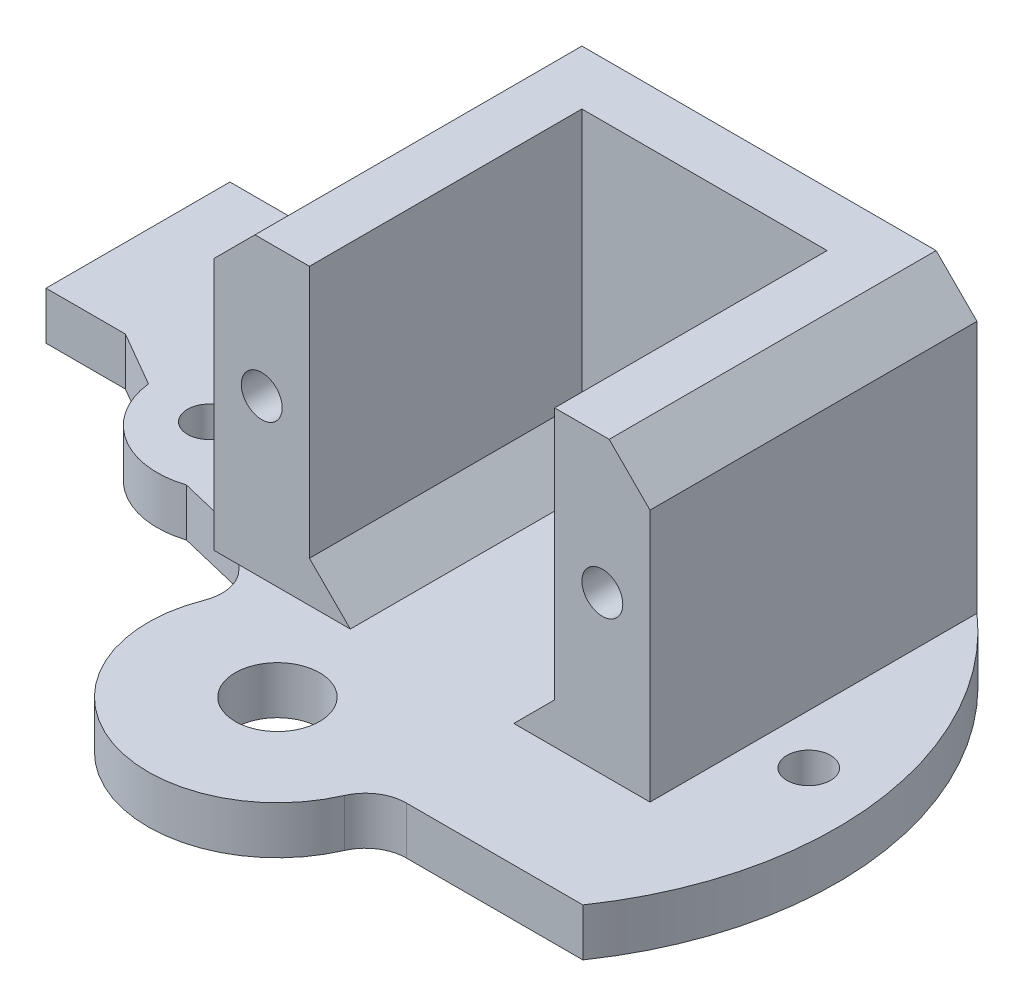
SolidWorks part; units mm, degrees
ref_plane "Alzado" through (0, 0, 0) normal (0, 0, 1) x (1, 0, 0)
ref_plane "Planta" through (0, 0, 0) normal (0, 1, 0) x (1, 0, 0)
ref_plane "Vista lateral" through (0, 0, 0) normal (1, 0, 0) x (0, 0, -1)
sketch "Croquis1" plane through (0, 0, 0) normal (0, 1, 0) x (1, 0, 0)
  line L0 (-35, 32.5) -> (35, -32.5) construction
  line L1 (-35, 32.5) -> (35, 32.5)
  line L2 (-35, 32.5) -> (-35, -32.5)
  line L3 (-35, -32.5) -> (35, -32.5)
  line L4 (35, 32.5) -> (35, -32.5)
  dimension "D1" = 70
  dimension "D2" = 65
extrude "Extruir1" add sketch "Croquis1" along normal blind 3.5
sketch "Croquis2" plane through (0, 3.5, 0) normal (0, 1, 0) x (1, 0, 0)
  line L0 (0, 32.5) -> (0, -32.5) construction
  line L1 (35, 32.5) -> (-35, 32.5) construction
  line L2 (-35, -32.5) -> (35, -32.5) construction
  circle A0 centre (0, -17.5) radius 3.1
  dimension "D1" = 6.2
  dimension "D2" = 15
extrude "Extruir2" cut sketch "Croquis2" against normal blind 5
sketch "Croquis3" plane through (0, 3.5, 0) normal (0, 1, 0) x (1, 0, 0)
  line L0 (0, -32.5) -> (0, 32.5) construction
  line L1 (-35, -32.5) -> (35, -32.5) construction
  line L2 (35, 32.5) -> (-35, 32.5) construction
  line L3 (-32.9868, -32.5) -> (-32.9868, 32.5) construction
  line L4 (-32.9868, 1.5) -> (-12.9615, 1.5)
  line L5 (18.8496, -32.5) -> (18.8496, 32.5) construction
  line L6 (-32.9868, 3.5) -> (18.8496, 3.5) construction
  line L7 (-32.9868, 2) -> (0, 2) construction
  line L8 (-32.9868, 11.5) -> (18.8496, 11.5) construction
  line L9 (0, -17.5) -> (-14.8492, -2.6508) construction
  line L10 (0, -17.5) -> (14.8492, -2.6508) construction
  line L11 (0, 2) -> (18.8496, 2) construction
  line L12 (-32.9868, 2) -> (18.8496, 2) construction
  line L13 (-32.9868, 12) -> (18.8496, 12)
  line L14 (-5.3033, -12.1967) -> (-16.2635, -1.2365) construction
  line L15 (12.9615, 1.5) -> (18.8496, 1.5)
  line L16 (-32.9868, 1.5) -> (18.8496, 1.5) construction
  line L17 (7.9844, -18) -> (22.9946, -18)
  line L18 (-5.9993, -12.2078) -> (-16.6132, -1.5939)
  line L19 (0, -17.5) -> (23, -17.5) construction
  line L20 (7.5, -17.5) -> (23, -17.5) construction
  line L21 (-5.6569, -12.5503) -> (-16.617, -1.5901) construction
  line L22 (7.5, -18) -> (23, -18) construction
  line L23 (-32.9868, 12) -> (-32.9868, 1.5)
  line L24 (18.8496, 12) -> (18.8496, 1.5)
  line L25 (-34.4868, 13.5) -> (20.3496, 13.5)
  line L26 (20.3496, 13.5) -> (20.3496, 0)
  line L27 (17.1464, 0) -> (20.3496, 0)
  line L28 (9.2871, -19.5) -> (24.4182, -19.5)
  line L29 (-7.9812, -12.3473) -> (-18.6805, -1.6479)
  line L30 (-34.4868, 0) -> (-17.1464, 0)
  line L31 (-34.4868, 13.5) -> (-34.4868, 0)
  circle A0 centre (0, -17.5) radius 21 construction
  circle A1 centre (0, -17.5) radius 7.5 construction
  arc A2 (-12.9615, 1.5) -> (-16.6132, -1.5939) centre (0, -17.5) ccw
  circle A3 centre (0, -17.5) radius 23 construction
  arc A4 (-5.9993, -12.2078) -> (7.9844, -18) centre (0, -17.5) ccw
  arc A5 (22.9946, -18) -> (12.9615, 1.5) centre (0, -17.5) ccw
  arc A6 (24.4182, -19.5) -> (17.1464, 0) centre (0, -17.5) ccw
  arc A7 (-7.9812, -12.3473) -> (9.2871, -19.5) centre (0, -17.5) ccw
  arc A8 (-17.1464, 0) -> (-18.6805, -1.6479) centre (0, -17.5) ccw
  dimension "D3" = 42
  dimension "D8" = 15
  dimension "D9" = 46
  dimension "D14" = 0.5
  dimension "D2" = 51.8364
  dimension "D6" = 90
  dimension "D7" = 45
  dimension "D1" = 32.9868
  dimension "D4" = 1.5
  dimension "D5" = 9.5
  dimension "D10" = 2
  dimension "D11" = 0.5
  dimension "D12" = 0.5
  dimension "D13" = 0.5
  dimension "D15" = 1.5
extrude "Extruir3" add sketch "Croquis3" along normal blind 10
sketch "Croquis4" plane through (0, 3.5, 0) normal (0, 1, 0) x (1, 0, 0)
  line L0 (-34.4868, 0) -> (-17.1464, 0) construction
  line L1 (-34.4868, 13.5) -> (-34.4868, 0) construction
  line L2 (20.3496, 13.5) -> (-34.4868, 13.5) construction
  line L3 (20.3496, 0) -> (20.3496, 13.5) construction
  line L4 (17.1464, 0) -> (20.3496, 0) construction
  line L5 (9.2871, -19.5) -> (24.4182, -19.5) construction
  line L6 (-18.6805, -1.6479) -> (-7.9812, -12.3473) construction
  line L7 (-34.4868, 0) -> (-17.1464, 0)
  line L8 (-34.4868, 13.5) -> (-34.4868, 0)
  line L9 (20.3496, 13.5) -> (-34.4868, 13.5)
  line L10 (20.3496, 0) -> (20.3496, 13.5)
  line L11 (17.1464, 0) -> (20.3496, 0)
  line L12 (9.2871, -19.5) -> (24.4182, -19.5)
  line L13 (-18.6805, -1.6479) -> (-7.9812, -12.3473)
  arc A0 (-17.1464, 0) -> (-18.6805, -1.6479) centre (0, -17.5) ccw construction
  arc A1 (24.4182, -19.5) -> (17.1464, 0) centre (0, -17.5) ccw construction
  arc A2 (-7.9812, -12.3473) -> (9.2871, -19.5) centre (0, -17.5) ccw construction
  arc A3 (-17.1464, 0) -> (-18.6805, -1.6479) centre (0, -17.5) ccw
  arc A4 (24.4182, -19.5) -> (17.1464, 0) centre (0, -17.5) ccw
  arc A5 (-7.9812, -12.3473) -> (9.2871, -19.5) centre (0, -17.5) ccw
extrude "Extruir4" cut sketch "Croquis4" against normal blind 10 flip side to cut
fillet "Redondeo1" radius 3 4 edges at (9.2871, 6.75, 19.5) (-7.9812, 6.75, 12.3473) (7.9844, 8.5, 18) (-5.9993, 8.5, 12.2078)
sketch "Croquis5" plane through (0, 0, 0) normal (0, -1, 0) x (1, 0, 0)
  line L0 (-18.6805, 1.6479) -> (-9.5151, 10.8133) construction
  line L1 (-34.4868, 0) -> (-17.1464, 0) construction
  line L2 (-18.6805, 1.6479) -> (-14.4379, 5.8906)
  line L3 (-24.4498, 0) -> (-17.1464, 0)
  line L4 (20.3496, 0) -> (20.3496, -13.5) construction
  line L5 (17.1464, 0) -> (20.3496, 0) construction
  line L6 (20.3496, 0) -> (20.3496, -13.5)
  line L7 (17.1464, 0) -> (20.3496, 0)
  arc A0 (-14.4379, 5.8906) -> (-24.4498, 0) centre (-18.6805, 1.6479) ccw
  arc A1 (-18.6805, 1.6479) -> (-17.1464, 0) centre (0, 17.5) ccw construction
  arc A2 (-18.6805, 1.6479) -> (-17.1464, 0) centre (0, 17.5) ccw
  arc A3 (24.4182, 19.5) -> (20.3496, -13.5) centre (3.8531, 5.2847) cw
  arc A4 (17.1464, 0) -> (24.4182, 19.5) centre (0, 17.5) ccw construction
  arc A5 (17.1464, 0) -> (24.4182, 19.5) centre (0, 17.5) ccw
  dimension "D1" = 12
  dimension "D2" = 25
extrude "Extruir5" add sketch "Croquis5" against normal up to surface (13.5 mm away) up to face at (-1.8278, 13.5, 5.5887)
chamfer "Chaflán1" distance 5 angle 45 2 edges at (-14.4379, 6.75, 5.8906) (-24.4498, 6.75, 0) first distance on face at (-20.5835, 6.75, 4.8823) first distance on face at (-29.4683, 6.75, 0)
sketch "Croquis6" plane through (0, 13.5, 0) normal (0, 1, 0) x (1, 0, 0)
  line L7 (-34.4868, 13.5) -> (-34.4868, 0)
  line L8 (-34.4868, 0) -> (-28.6614, 0)
  line L9 (-28.6614, 0) -> (-24.6424, -2.3231)
  line L10 (-16.83, -7.3554) -> (-11.7523, -8.5761)
  line L11 (-11.7523, -8.5761) -> (-9.5151, -10.8133)
  line L12 (11.4564, -19.5) -> (24.4182, -19.5)
  line L13 (20.3496, 13.5) -> (-34.4868, 13.5)
  line L14 (-34.4868, 13.5) -> (-34.4868, 0)
  line L15 (-34.4868, 0) -> (-28.6614, 0)
  line L16 (-28.6614, 0) -> (-24.6424, -2.3231)
  line L17 (-16.83, -7.3554) -> (-11.7523, -8.5761)
  line L18 (-11.7523, -8.5761) -> (-9.5151, -10.8133)
  line L19 (11.4564, -19.5) -> (24.4182, -19.5)
  line L20 (20.3496, 13.5) -> (-34.4868, 13.5)
  arc A5 (-24.6424, -2.3231) -> (-16.83, -7.3554) centre (-18.6805, -1.6479) ccw
  arc A6 (-8.8437, -14.0303) -> (-9.5151, -10.8133) centre (-11.6365, -12.9346) ccw
  arc A7 (-8.8437, -14.0303) -> (8.7069, -21.3) centre (0, -17.5) ccw
  arc A8 (11.4564, -19.5) -> (8.7069, -21.3) centre (11.4564, -22.5) ccw
  arc A9 (24.4182, -19.5) -> (20.3496, 13.5) centre (3.8531, -5.2847) ccw
  arc A10 (-24.6424, -2.3231) -> (-16.83, -7.3554) centre (-18.6805, -1.6479) ccw
  arc A11 (-8.8437, -14.0303) -> (-9.5151, -10.8133) centre (-11.6365, -12.9346) ccw
  arc A12 (-8.8437, -14.0303) -> (8.7069, -21.3) centre (0, -17.5) ccw
  arc A13 (11.4564, -19.5) -> (8.7069, -21.3) centre (11.4564, -22.5) ccw
  arc A14 (24.4182, -19.5) -> (20.3496, 13.5) centre (3.8531, -5.2847) ccw
  dimension "D1" = 0
extrude "Extruir6" add sketch "Croquis6" along normal blind 3.5 separate body
sketch "Croquis7" plane through (0, 17, 0) normal (0, 1, 0) x (1, 0, 0)
  line L0 (20.3496, 13.5) -> (-34.4868, 13.5) construction
  circle A0 centre (-20, -2.5) radius 1.6
  circle A1 centre (24, -2.5) radius 1.6
  dimension "D1" = 3.2
  dimension "D2" = 16
  dimension "D3" = 20
  dimension "D4" = 24
extrude "Extruir7" cut sketch "Croquis7" against normal through all
sketch "Croquis8" plane through (0, 17, 0) normal (0, 1, 0) x (1, 0, 0)
  circle A0 centre (0, -17.5) radius 3.1 construction
  circle A1 centre (0, -17.5) radius 3.1
extrude "Extruir8" cut sketch "Croquis8" against normal blind 5
sketch "Croquis9" plane through (0, 13.5, 0) normal (0, 1, 0) x (1, 0, 0)
  line L0 (18.8496, 1.5) -> (18.8496, 12) construction
  line L1 (18.8496, 1.5) -> (18.8496, 12)
  line L2 (19.5496, 1.5) -> (19.5496, 12)
  line L3 (18.8496, 12) -> (19.5496, 12)
  line L4 (18.8496, 1.5) -> (19.5496, 1.5)
  dimension "D1" = 0.7
extrude "Extruir9" cut sketch "Croquis9" against normal up to surface (10 mm away) up to face at (-1.6185, 3.5, 4.8365)
sketch "Croquis10" plane through (19.5496, 0, 0) normal (-1, 0, 0) x (0, 0, 1)
  line L0 (-5.875, 13.5) -> (-5.875, 3.5) construction
  line L3 (-1.5, 13.5) -> (-12, 13.5) construction
  line L4 (-12, 3.5) -> (-12, 13.5) construction
  line L5 (-5.875, 13.5) -> (-12, 3.5) construction
  line L6 (-12, 3.5) -> (-1.5, 3.5) construction
  line L7 (-8.9375, 8.5) -> (-12, 13.5) construction
  line L8 (19.5, 13.5) -> (-13.5, 13.5) construction
  line L10 (-7.4062, 11) -> (-10.4687, 11)
  line L11 (-7.4062, 11) -> (-7.4062, 6)
  line L12 (-7.4062, 6) -> (-10.4687, 6)
  line L13 (-10.4687, 11) -> (-10.4687, 6)
  dimension "D1" = 6.125
  dimension "D2" = 5
  dimension "D3" = 3.0625
extrude "Extruir10" cut sketch "Croquis10" against normal blind 10 and the other way through all
delete or keep bodies "Sólido-Eliminar1" type delete bodies bodies 111
sketch "Croquis11" plane through (0, 0, -13.5) normal (0, 0, -1) x (-1, 0, 0)
  line L0 (34.4868, 17) -> (34.4868, 47)
  line L1 (34.4868, 47) -> (-20.3496, 47)
  line L2 (-20.3496, 47) -> (-20.3496, 17)
  line L3 (-20.3496, 17) -> (34.4868, 17)
  dimension "D1" = 30
  dimension "D2" = 30
extrude "Saliente-Extruir1" add sketch "Croquis11" against normal blind 4
sketch "Croquis13" plane through (0, 0, -9.5) normal (0, 0, 1) x (1, 0, 0)
  line L0 (-11.6504, 47) -> (-4.6504, 47)
  line L1 (-34.4868, 47) -> (20.3496, 47) construction
  line L2 (-4.6504, 47) -> (-4.6504, 17)
  line L3 (8.7069, 17) -> (-9.5, 17) construction
  line L4 (20.3496, 47) -> (13.3496, 47)
  line L5 (13.3496, 47) -> (13.3496, 17)
  line L6 (-11.6504, 47) -> (-11.6504, 17)
  line L7 (20.3496, 17) -> (-34.4868, 17) construction
  line L8 (-11.6504, 17) -> (-4.6504, 17)
  line L9 (13.3496, 17) -> (20.3496, 17)
  line L10 (20.3496, 17) -> (20.3496, 47)
  line L11 (16.8496, 17) -> (16.8496, 47) construction
  line L13 (-8.1504, 17) -> (-8.1504, 47) construction
  dimension "D1" = 7
  dimension "D2" = 7
  dimension "D3" = 25
extrude "Saliente-Extruir2" add sketch "Croquis13" along normal blind 20
sketch "Croquis14" plane through (0, 47, 0) normal (0, 1, 0) x (1, 0, 0)
  line L10 (20.3496, 13.5) -> (-34.4868, 13.5)
  line L11 (-34.4868, 13.5) -> (-34.4868, 9.5)
  line L12 (-34.4868, 9.5) -> (-11.6504, 9.5)
  line L13 (-11.6504, 9.5) -> (-11.6504, -10.5)
  line L14 (-11.6504, -10.5) -> (-4.6504, -10.5)
  line L15 (-4.6504, -10.5) -> (-4.6504, 9.5)
  line L16 (-4.6504, 9.5) -> (13.3496, 9.5)
  line L17 (13.3496, 9.5) -> (13.3496, -10.5)
  line L18 (13.3496, -10.5) -> (20.3496, -10.5)
  line L19 (20.3496, -10.5) -> (20.3496, 13.5)
  line L20 (20.3496, 13.5) -> (-34.4868, 13.5)
  line L21 (-34.4868, 13.5) -> (-34.4868, 9.5)
  line L22 (-34.4868, 9.5) -> (-11.6504, 9.5)
  line L23 (-11.6504, 9.5) -> (-11.6504, -10.5)
  line L24 (-11.6504, -10.5) -> (-4.6504, -10.5)
  line L25 (-4.6504, -10.5) -> (-4.6504, 9.5)
  line L26 (-4.6504, 9.5) -> (13.3496, 9.5)
  line L27 (13.3496, 9.5) -> (13.3496, -10.5)
  line L28 (13.3496, -10.5) -> (20.3496, -10.5)
  line L29 (20.3496, -10.5) -> (20.3496, 13.5)
  dimension "D1" = 0
extrude "Cortar-Extruir1" cut sketch "Croquis14" against normal blind 8.44
sketch "Croquis15" plane through (0, 0, -9.5) normal (0, 0, 1) x (1, 0, 0)
  line L4 (-11.6504, 38.56) -> (-34.4868, 38.56)
  line L5 (-34.4868, 38.56) -> (-34.4868, 17)
  line L6 (-34.4868, 17) -> (-11.6504, 17)
  line L7 (-11.6504, 17) -> (-11.6504, 38.56)
  line L8 (-11.6504, 38.56) -> (-34.4868, 38.56)
  line L9 (-34.4868, 38.56) -> (-34.4868, 17)
  line L10 (-34.4868, 17) -> (-11.6504, 17)
  line L11 (-11.6504, 17) -> (-11.6504, 38.56)
  dimension "D1" = 0
extrude "Cortar-Extruir2" cut sketch "Croquis15" against normal blind 8.44
chamfer "Chaflán2" distance 3 angle 45 3 edges at (13.3496, 17, 0.5) (-4.6504, 17, 0.5)
sketch "Croquis16" plane through (0, 0, 10.5) normal (0, 0, 1) x (1, 0, 0)
  line L0 (-8.1504, 17) -> (-8.1504, 47) construction
  line L1 (16.8496, 17) -> (16.8496, 47) construction
  line L2 (-11.6504, 38.56) -> (-4.6504, 38.56) construction
  circle A0 centre (-8.1504, 28.56) radius 1.5
  circle A1 centre (16.8496, 28.56) radius 1.5
  dimension "D1" = 3
  dimension "D2" = 10
extrude "Cortar-Extruir3" cut sketch "Croquis16" against normal through all
chamfer "Chaflán3" distance 3 angle 45 2 edges at (20.3496, 38.56, -1.5) (-11.6504, 38.56, -1.5)
move or copy body "Sólido-Mover/Copiar1" [suppressed] bodies to move or copy 117
